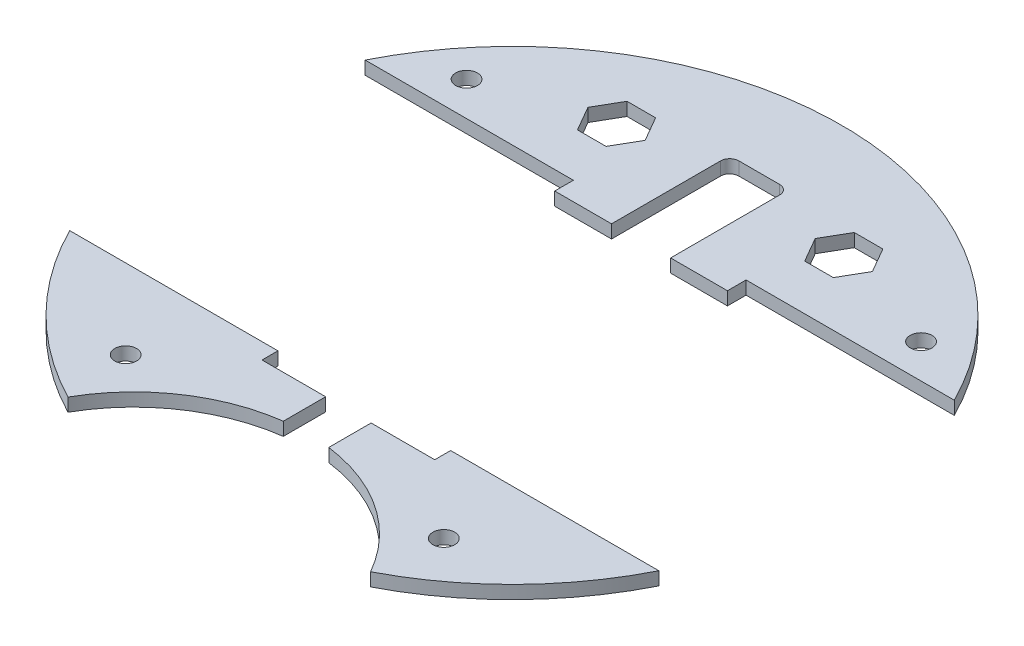
SolidWorks part; units mm, degrees
material "Acrylic (Medium-high impact)"
ref_plane "Front Plane" through (0, 0, 0) normal (0, 0, 1) x (1, 0, 0)
ref_plane "Top Plane" through (0, 0, 0) normal (0, 1, 0) x (1, 0, 0)
ref_plane "Right Plane" through (0, 0, 0) normal (1, 0, 0) x (0, 0, -1)
sketch "Sketch1" plane through (0, 0, 0) normal (0, 1, 0) x (1, 0, 0)
  line L0 (0, -83.2398) -> (-33.2911, -64.4046) construction
  line L1 (0, -83.2398) -> (0, 0) construction
  arc A0 (33.2911, -64.4046) -> (-33.2911, -64.4046) centre (0, 0) ccw
  arc A1 (33.2911, -64.4046) -> (-33.2911, -64.4046) centre (0, -83.2398) ccw
  dimension "D1" = 145
  dimension "D2" = 76.5
  dimension "D3" = 60.5
extrude "Boss-Extrude1" add sketch "Sketch1" along normal blind 2.9
sketch "solenoid placement" plane through (0, 2.9, 0) normal (0, 1, 0) x (1, 0, 0)
  line L4 (-19, -36) -> (19, -36)
  line L5 (-19, 28.4) -> (-19, -36)
  line L6 (19, 28.4) -> (-19, 28.4)
  line L7 (19, -36) -> (19, 28.4)
  line L8 (-19, -36) -> (19, -36)
  line L9 (-19, 28.4) -> (-19, -36)
  line L10 (19, 28.4) -> (-19, 28.4)
  line L11 (19, -36) -> (19, 28.4)
  dimension "D1" = 0
extrude "Cut-Extrude1" cut sketch "solenoid placement" against normal through all
sketch "Sketch4" plane through (0, 2.9, 0) normal (0, 1, 0) x (1, 0, 0)
  line L6 (-6.5, 28.1) -> (6.5, 28.1)
  line L7 (6.5, 28.1) -> (6.5, 52.4)
  line L8 (4.5, 54.4) -> (-4.5, 54.4)
  line L9 (-6.5, 52.4) -> (-6.5, 28.1)
  line L10 (-6.5, 28.1) -> (6.5, 28.1)
  line L11 (6.5, 28.1) -> (6.5, 52.4)
  line L12 (4.5, 54.4) -> (-4.5, 54.4)
  line L13 (-6.5, 52.4) -> (-6.5, 28.1)
  arc A4 (6.5, 52.4) -> (4.5, 54.4) centre (4.5, 52.4) ccw
  arc A5 (6.5, 52.4) -> (4.5, 54.4) centre (4.5, 52.4) ccw
  arc A6 (-4.5, 54.4) -> (-6.5, 52.4) centre (-4.5, 52.4) ccw
  arc A7 (-4.5, 54.4) -> (-6.5, 52.4) centre (-4.5, 52.4) ccw
  dimension "D1" = 0
extrude "Cut-Extrude4" cut sketch "Sketch4" against normal through all
sketch "Sketch5" plane through (0, 2.9, 0) normal (0, 1, 0) x (1, 0, 0)
  line L6 (-18.7069, 48) -> (-21.8534, 53.45)
  line L7 (-21.8534, 53.45) -> (-28.1466, 53.45)
  line L8 (-28.1466, 53.45) -> (-31.2931, 48)
  line L9 (-31.2931, 48) -> (-28.1466, 42.55)
  line L10 (-28.1466, 42.55) -> (-21.8534, 42.55)
  line L11 (-21.8534, 42.55) -> (-18.7069, 48)
  line L12 (-18.7069, 48) -> (-21.8534, 53.45)
  line L13 (-21.8534, 53.45) -> (-28.1466, 53.45)
  line L14 (-28.1466, 53.45) -> (-31.2931, 48)
  line L15 (-31.2931, 48) -> (-28.1466, 42.55)
  line L16 (-28.1466, 42.55) -> (-21.8534, 42.55)
  line L17 (-21.8534, 42.55) -> (-18.7069, 48)
  line L18 (18.7069, 48) -> (21.8534, 42.55)
  line L19 (21.8534, 53.45) -> (18.7069, 48)
  line L20 (28.1466, 53.45) -> (21.8534, 53.45)
  line L21 (31.2931, 48) -> (28.1466, 53.45)
  line L22 (28.1466, 42.55) -> (31.2931, 48)
  line L23 (21.8534, 42.55) -> (28.1466, 42.55)
  line L24 (18.7069, 48) -> (21.8534, 42.55)
  line L25 (21.8534, 53.45) -> (18.7069, 48)
  line L26 (28.1466, 53.45) -> (21.8534, 53.45)
  line L27 (31.2931, 48) -> (28.1466, 53.45)
  line L28 (28.1466, 42.55) -> (31.2931, 48)
  line L29 (21.8534, 42.55) -> (28.1466, 42.55)
  dimension "D1" = 0
  dimension "D2" = 0
extrude "Cut-Extrude5" cut sketch "Sketch5" against normal through all
sketch "Sketch6" plane through (0, 2.9, 0) normal (0, 1, 0) x (1, 0, 0)
  circle A1 centre (35, -50) radius 2.4
  circle A2 centre (35, -50) radius 2.4
  circle A3 centre (-35, -50) radius 2.4
  circle A4 centre (-35, -50) radius 2.4
  circle A5 centre (-50, 40) radius 2.4
  circle A6 centre (-50, 40) radius 2.4
  circle A7 centre (50, 40) radius 2.4
  circle A8 centre (50, 40) radius 2.4
  dimension "D1" = 0
  dimension "D2" = 0
  dimension "D3" = 0
  dimension "D4" = 0
extrude "Cut-Extrude6" cut sketch "Sketch6" against normal through all
sketch "Sketch3" plane through (0, 2.9, 0) normal (0, 1, 0) x (1, 0, 0)
  line L0 (-19, 28.4) -> (-19, 32.5)
  line L1 (72.5, -32.5) -> (-72.5, -32.5)
  line L2 (72.5, -32.5) -> (72.5, 32.5)
  line L3 (72.5, 32.5) -> (19, 32.5)
  line L4 (-72.5, -32.5) -> (-72.5, 32.5)
  line L5 (72.5, -32.5) -> (-72.5, 32.5) construction
  line L6 (72.5, 32.5) -> (-72.5, -32.5) construction
  line L7 (-19, 28.4) -> (19, 28.4)
  line L8 (19, 28.4) -> (19, 32.5)
  line L9 (-19, 32.5) -> (-72.5, 32.5)
  arc A0 (33.2911, -64.4046) -> (-33.2911, -64.4046) centre (0, 0) ccw construction
  point P0 (0, 0)
  dimension "D1" = 65
extrude "Cut-Extrude3" cut sketch "Sketch3" against normal through all
sketch "Sketch7" plane through (0, 2.9, 0) normal (0, 1, 0) x (1, 0, 0)
  line L4 (5, 0) -> (-5, 0)
  line L5 (5, -62.8025) -> (5, 0)
  line L6 (-5, -62.8025) -> (5, -62.8025)
  line L7 (-5, 0) -> (-5, -62.8025)
  line L8 (5, 0) -> (-5, 0)
  line L9 (5, -62.8025) -> (5, 0)
  line L10 (-5, -62.8025) -> (5, -62.8025)
  line L11 (-5, 0) -> (-5, -62.8025)
  dimension "D1" = 0
extrude "Cut-Extrude7" cut sketch "Sketch7" against normal through all
equation "\"smallPulleyTeeth\"= 15"
equation "\"largePulleyTeeth\"= 30"
equation "\"eighthThick\"= 2.9mm"
equation "\"sixteenthThick\" = 1.7mm"
equation "\"quarterThick\"=6.0mm"
equation "\"OD\" = 145mm"
equation "\"puckAngle\" = 60.5deg"
equation "\"D1@Sketch1\"=\"OD\""
equation "\"puckDiam\" = 76.5mm"
equation "\"D2@Sketch1\"=\"puckDiam\""
equation "\"D3@Sketch1\"=\"puckAngle\""
equation "\"D1@Boss-Extrude1\"=\"eighthThick\""
equation "\"axlePress\" = 5.9mm"
equation "\"press\" = 0.2mm"
equation "\"wheelClear\" = 0.3mm"
equation "\"10-32clear\" = 4.8mm"
equation "\"6-32clear\" = 3.3mm"
equation "\"8-32clear\" = 4.0mm"
equation "\"wheelHeight\" = 22mm"
equation "\"wheelWell\" = 65mm"
equation "\"D1@Sketch3\"=\"wheelWell\""
